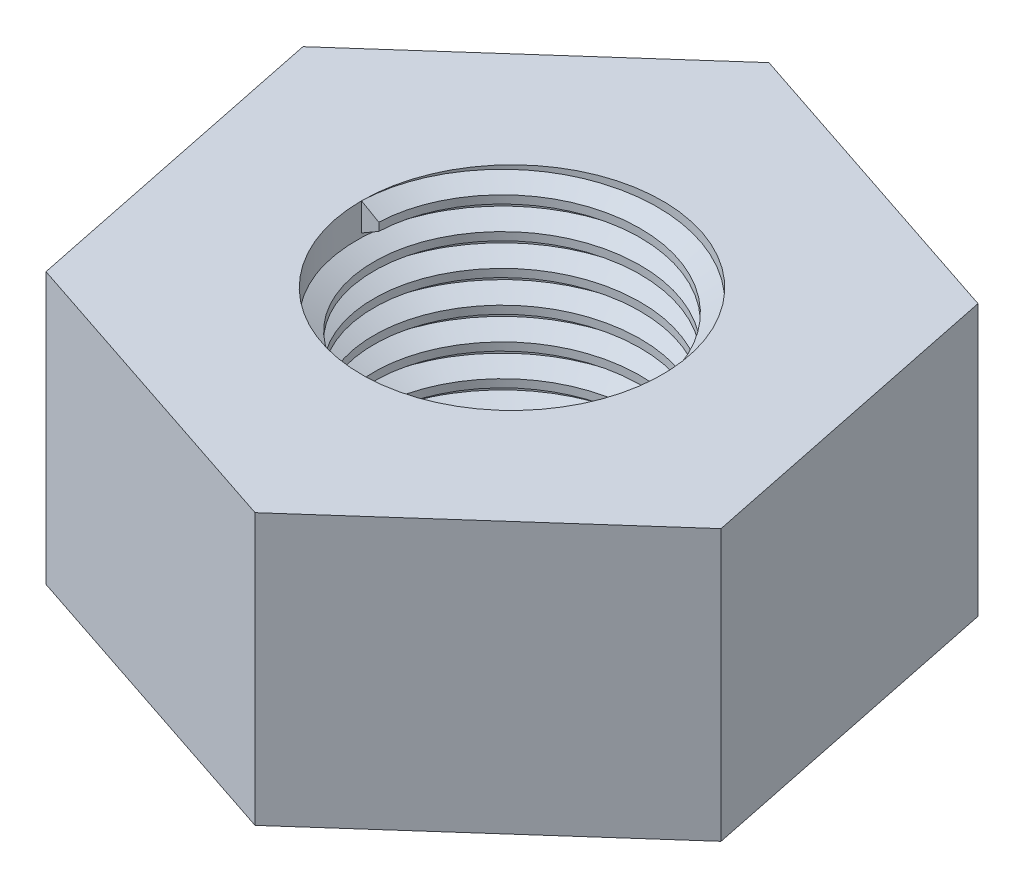
SolidWorks part; units mm, degrees
ref_plane "Front Plane" through (0, 0, 0) normal (0, 0, 1) x (1, 0, 0)
ref_plane "Top Plane" through (0, 0, 0) normal (0, 1, 0) x (1, 0, 0)
ref_plane "Right Plane" through (0, 0, 0) normal (1, 0, 0) x (0, 0, -1)
sketch "Sketch1" plane through (0, 0, 0) normal (0, 1, 0) x (1, 0, 0)
  line L1 (8.2027, 7.2835) -> (-2.2063, 10.7455)
  line L2 (-2.2063, 10.7455) -> (-10.409, 3.462)
  line L3 (-10.409, 3.462) -> (-8.2027, -7.2835)
  line L4 (-8.2027, -7.2835) -> (2.2063, -10.7455)
  line L5 (2.2063, -10.7455) -> (10.409, -3.462)
  line L6 (10.409, -3.462) -> (8.2027, 7.2835)
  circle A0 centre (0, 0) radius 9.5 construction
  circle A1 centre (0, 0) radius 5
  dimension "D2" = 10
  dimension "D1" = 19
base flange "Base-Flange1" sketch "Sketch1" thickness 9 reverse thickness direction no parameters "D1"=5
thread "Thread1" pitch 1.0583 start angle 0, offset 0, length 9, pitch 1.0583, diameter 10
ref_plane "Plane1" through (-5, 0, 0) normal (0, 0, 1) x (-1, 0, 0)
sketch "Thread Profile1" plane through (-5, 0, 0) normal (0, 0, 1) x (-1, 0, 0)
  line L0 (0, 0) -> (0, 1.0583) construction
  line L11 (0, 0) -> (0, 0.926)
  line L12 (0, 0.926) -> (-0.5728, 0.5953)
  line L13 (-0.5728, 0.5953) -> (-0.5728, 0.3307)
  line L15 (-0.5728, 0.3307) -> (0, 0)
  line L17 (-0.5728, 0.463) -> (0, 0.463) construction
  point P2 (0, 0)
  dimension "Pitch" = 1.0583
  dimension "Profile_Angle" = 60
  dimension "Profile_Land" = 0.2646
  dimension "Profile_Height" = 0.5728
sketch "Bend-Lines1" [suppressed] plane through (0, 0, 0) normal (0, 1, 0) x (1, 0, 0)
sketch "Bounding-Box1" [suppressed] plane through (0, 0, 0) normal (0, 1, 0) x (1, 0, 0)
sheet metal parameters "Sheet-Metal1" thickness 9 parameters "D1"=5
flat pattern "Flat-Pattern1" [suppressed]
sketch "Bend-Lines2" plane through (0, 0, 0) normal (0, 1, 0) x (1, 0, 0)
sketch3d "Bounding-Box2" [suppressed]
  line L0 (11.5122, 8.8348, 0) -> (7.0996, -12.6562, 0) construction
  line L1 (-7.0996, 12.6562, 0) -> (-11.5122, -8.8348, 0) construction
  line L2 (11.5122, 8.8348, 0) -> (-7.0996, 12.6562, 0) construction
  line L3 (7.0996, -12.6562, 0) -> (-11.5122, -8.8348, 0) construction
sheet metal parameters "Sheet-Metal2" thickness 9 parameters "D1"=5
flat pattern "Flat-Pattern1"
sketch "Bend-Lines2" plane through (0, 0, 0) normal (0, 1, 0) x (1, 0, 0)
sketch3d "Bounding-Box2" [suppressed]
  line L0 (-11.5122, 8.8348, 0) -> (-7.0996, -12.6562, 0) construction
  line L1 (7.0996, 12.6562, 0) -> (11.5122, -8.8348, 0) construction
  line L2 (-11.5122, 8.8348, 0) -> (7.0996, 12.6562, 0) construction
  line L3 (-7.0996, -12.6562, 0) -> (11.5122, -8.8348, 0) construction
